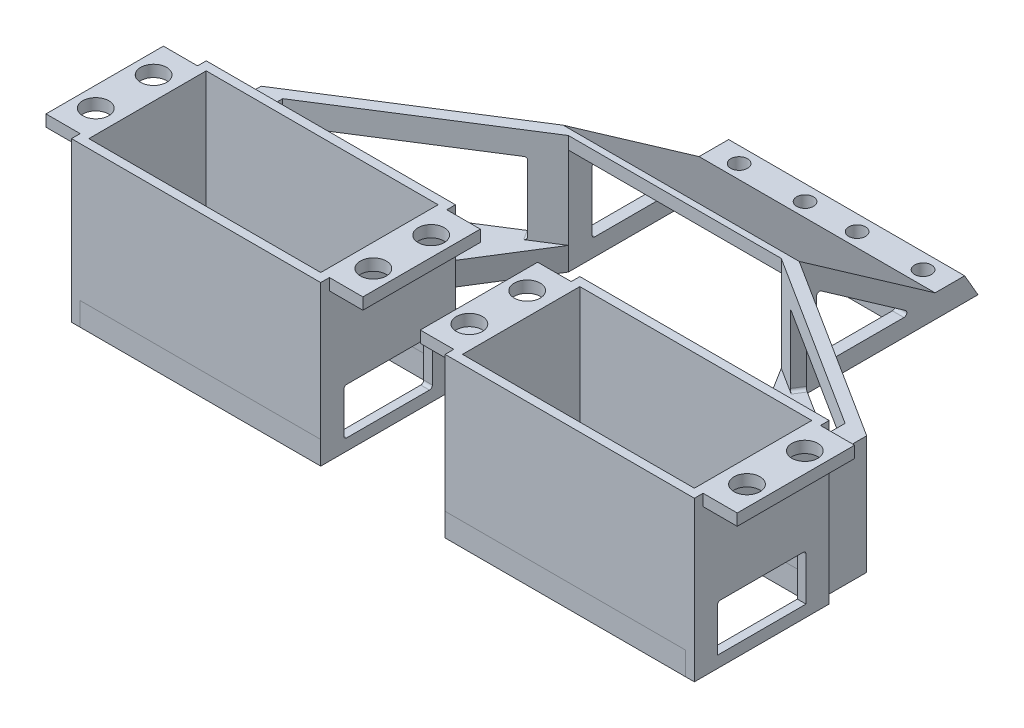
SolidWorks part; units mm, degrees
ref_plane "Front Plane" through (0, 0, 0) normal (0, 0, 1) x (1, 0, 0)
ref_plane "Top Plane" through (0, 0, 0) normal (0, 1, 0) x (1, 0, 0)
ref_plane "Right Plane" through (0, 0, 0) normal (1, 0, 0) x (0, 0, -1)
sketch "Sketch1" plane through (0, 0, 0) normal (0, 1, 0) x (1, 0, 0)
  line L0 (-59.76, 0) -> (59.76, 0) construction
  line L1 (0, -47.12) -> (0, 47.12) construction
  line L2 (-52.3548, -33.8709) -> (-52.3524, -13.5709)
  line L5 (-52.3524, -13.5709) -> (-12.2524, -13.5757)
  line L8 (-59.76, -47.12) -> (-59.76, -23.72) construction
  line L9 (-59.76, -47.12) -> (59.76, -47.12) construction
  line L10 (-59.76, -47.12) -> (-59.76, 47.12) construction
  line L11 (-59.76, 47.12) -> (59.76, 47.12) construction
  line L12 (59.76, -47.12) -> (59.76, 47.12) construction
  line L13 (-12.2524, -13.5757) -> (-12.2548, -33.8757)
  line L14 (-12.2548, -33.8757) -> (-52.3548, -33.8709)
  line L15 (-53.8522, -12.0707) -> (-10.7522, -12.0759)
  line L16 (-10.7522, -12.0759) -> (-10.755, -35.3759)
  line L17 (-10.755, -35.3759) -> (-53.855, -35.3707)
  line L18 (-53.855, -35.3707) -> (-53.8522, -12.0707)
  line L19 (-52.3524, -12.0709) -> (-52.3524, -4.0757)
  line L20 (-52.3524, -4.0757) -> (-12.2524, -4.0757)
  line L21 (-12.2524, -4.0757) -> (-12.2524, -12.0757)
  line L22 (-52.3548, -35.3709) -> (-52.3548, -43.3757)
  line L23 (-52.3548, -43.3757) -> (-12.2548, -43.3757)
  line L24 (-12.2548, -43.3757) -> (-12.2548, -35.3757)
  line L25 (-20.4049, 47.12) -> (0, 47.12)
  line L26 (-20.4049, 47.12) -> (-20.4049, 16.2008)
  line L27 (-20.4049, 16.2008) -> (-52.3524, -4.0757)
  line L28 (0, 47.12) -> (0, 45.12)
  line L29 (0, 45.12) -> (-18.4049, 45.12)
  line L30 (-18.4049, 45.12) -> (-18.4049, 15.1014)
  line L31 (-18.4049, 15.1014) -> (-48.6201, -4.0757)
  point P5 (0, 0)
  point P6 (0, 0)
  point P7 (-59.76, -23.72)
  point P32 (0, 47.12)
  line B0 (-52.3548, -33.8709) -> (-52.3524, -13.5709) construction
  line B1 (-4.9588, -13.5765) -> (-59.7588, -13.57) construction
  line B2 (-4.9612, -33.8765) -> (-4.9588, -13.5765) construction
  line B3 (-12.2548, -33.8757) -> (-12.2524, -13.5757) construction
  line B4 (-4.9612, -33.8765) -> (-59.7612, -33.87) construction
  line B5 (-59.7588, -13.57) -> (-59.7612, -33.87) construction
  circle B6 centre (-8.3042, -28.7261) radius 2.25 construction
  circle B7 centre (-8.303, -18.7261) radius 2.25 construction
  circle B8 centre (-56.303, -18.7204) radius 2.25 construction
  circle B9 centre (-56.3042, -28.7204) radius 2.25 construction
  dimension "D1" = 119.52
  dimension "D2" = 94.24
  dimension "D3" = 1.5
  dimension "D4" = 23.4
  dimension "D5" = 8
  dimension "D6" = 8
  dimension "D7" = 2
  dimension "D8" = 2
  dimension "D9" = 2
sketch_block_instance "Block2-1"
sketch_block "Block2"
extrude "Boss-Extrude1" add sketch "Sketch1" along normal blind 4 contours L31 L30 L29 L28 L25 L26 L27 L20 | L21 L20 L19 L15 | L18 L17 L16 L15 L13 L14 L2 L5 | L23 L24 L17 L22 region at (-53.1023, 0, 12.5608) region at (-32.3004, 0, 8.0745) region at (-35.9862, 0, -5.4443) region at (-32.3068, 0, 39.3745)
sketch "Sketch2" plane through (0, 4, 0) normal (0, 1, 0) x (1, 0, 0)
  line L1 (-48.6201, -4.0757) -> (-18.4049, 15.1014)
  line L2 (-18.4049, 15.1014) -> (-18.4049, 45.12)
  line L3 (-18.4049, 45.12) -> (0, 45.12)
  line L4 (0, 45.12) -> (0, 47.12)
  line L5 (0, 47.12) -> (-20.4049, 47.12)
  line L6 (-20.4049, 47.12) -> (-20.4049, 16.2008)
  line L7 (-20.4049, 16.2008) -> (-52.3524, -4.0757)
  line L8 (-53.8522, -12.0707) -> (-10.7522, -12.0759)
  line L9 (-10.7522, -12.0759) -> (-10.755, -35.3759)
  line L10 (-10.755, -35.3759) -> (-53.855, -35.3707)
  line L11 (-53.855, -35.3707) -> (-53.8522, -12.0707)
  line L12 (-48.6201, -4.0757) -> (-48.6201, -12.0713)
  line L13 (-52.3548, -33.8709) -> (-12.2524, -33.8709)
  line L14 (-52.3548, -33.8709) -> (-52.3548, -13.5757)
  line L15 (-52.3548, -13.5757) -> (-12.2524, -13.5757)
  line L16 (-12.2524, -33.8709) -> (-12.2524, -13.5757)
  line L17 (-52.3524, -4.0757) -> (-52.3524, -12.0709)
  point P30 (0, 0)
  line M1 (-48.6201, -4.0757) -> (-18.4049, 15.1014)
  line M2 (-18.4049, 15.1014) -> (-18.4049, 45.12)
  line M3 (-18.4049, 45.12) -> (0, 45.12)
  line M4 (0, 45.12) -> (0, 47.12)
  line M5 (0, 47.12) -> (-20.4049, 47.12)
  line M6 (-20.4049, 47.12) -> (-20.4049, 16.2008)
  line M7 (-20.4049, 16.2008) -> (-52.3524, -4.0757)
  line M8 (-52.3524, -4.0757) -> (-52.3524, -12.0709)
extrude "Boss-Extrude3" add sketch "Sketch2" along normal blind 23.5 contours L12 L8 M1 M2 M3 M4 M5 M6 M7 M8 | L8 L9 L10 L11 | L14 L15 L16 L13 region at (-49.4103, 4, 8.0735)
sketch "Sketch4" plane through (0, 27.5, 0) normal (0, 1, 0) x (1, 0, 0)
  line L0 (-52.3548, -13.5757) -> (-59.7588, -13.57)
  line L1 (-59.7588, -13.57) -> (-59.7612, -33.87)
  line L2 (-59.7612, -33.87) -> (-52.3548, -33.8709)
  line L3 (-12.2524, -13.5757) -> (-4.9588, -13.5765)
  line L4 (-4.9588, -13.5765) -> (-4.9612, -33.8765)
  line L5 (-4.9612, -33.8765) -> (-12.2524, -33.8709)
  line L6 (-12.2524, -33.8709) -> (-12.2524, -13.5757)
  line L7 (-52.3548, -33.8709) -> (-52.3548, -13.5757)
  circle A0 centre (-56.303, -18.7204) radius 2.25
  circle A1 centre (-56.3042, -28.7204) radius 2.25
  circle A2 centre (-8.303, -18.7261) radius 2.25
  circle A3 centre (-8.3042, -28.7261) radius 2.25
extrude "Boss-Extrude4" add sketch "Sketch4" against normal blind 2
sketch "Sketch5" plane through (-10.7507, 0, -0.0013) normal (1, 0, 0.0001) x (0.0001, 0, -1)
  line L1 (-31.3771, 2) -> (-16.0771, 2)
  line L2 (-31.3771, 2) -> (-31.3771, 10)
  line L3 (-31.3771, 10) -> (-16.0771, 10)
  line L4 (-16.0771, 2) -> (-16.0771, 10)
  line L6 (-35.3771, 27.5) -> (-35.3771, 0) construction
  line L7 (-12.0771, 27.5) -> (-12.0771, 0) construction
  line L8 (-13.5771, 0) -> (-33.8771, 0) construction
  dimension "D1" = 4
  dimension "D2" = 4
  dimension "D3" = 2
  dimension "D4" = 8
extrude "Cut-Extrude1" cut sketch "Sketch5" against normal through all
sketch "Sketch6" plane through (0, 4, 0) normal (0, 1, 0) x (1, 0, 0)
  line L0 (-52.3548, -43.3757) -> (-12.2548, -43.3757) construction
  line L1 (-12.2548, -43.3757) -> (-12.2548, -35.3757) construction
  line L2 (-52.3548, -35.3709) -> (-52.3548, -43.3757) construction
  line L3 (-52.3524, -12.0709) -> (-52.3524, -4.0757) construction
  line L4 (-52.3524, -4.0757) -> (-12.2524, -4.0757) construction
  line L5 (-12.2524, -4.0757) -> (-12.2524, -12.0757) construction
  circle A0 centre (-44.3548, -39.3757) radius 1.45
  circle A1 centre (-20.2548, -39.3757) radius 1.45
  circle A2 centre (-44.3524, -8.0757) radius 1.45
  circle A3 centre (-20.2524, -8.0757) radius 1.45
  dimension "D1" = 2.9
  dimension "D2" = 2.9
  dimension "D4" = 8
  dimension "D5" = 8
  dimension "D6" = 4
  dimension "D7" = 2.9
  dimension "D8" = 8
  dimension "D9" = 4
  dimension "D10" = 2.9
  dimension "D11" = 8
  dimension "D12" = 4
  dimension "D3" = 4
extrude "Cut-Extrude2" cut sketch "Sketch6" against normal through all
sketch "Sketch7" plane through (-20.4049, 0, 0) normal (-1, 0, 0) x (0, 0, 1)
  line L1 (-39.7008, 4) -> (-16.2008, 20.4549)
  line L3 (-16.2008, 27.5) -> (-16.2008, 0) construction
  line L5 (-16.2008, 20.4549) -> (12.0708, 20.4549)
  line L7 (12.0709, 38.4434) -> (-47.12, 27.5)
  line L8 (-47.12, 0) -> (-16.2008, 0) construction
  line L9 (-47.12, 4) -> (-39.7008, 4)
  line L10 (-47.12, 27.5) -> (-47.12, 0) construction
  line L13 (-47.12, 27.5) -> (-47.12, 4)
  line L14 (12.0709, 38.4434) -> (12.0707, 27.5)
  line L19 (12.0708, 20.4549) -> (12.0707, 27.5)
  dimension "D1" = 4
  dimension "D2" = 145
extrude "Cut-Extrude3" cut sketch "Sketch7" against normal through all and the other way through all
sketch "Sketch8" plane through (-20.4049, 0, 0) normal (-1, 0, 0) x (0, 0, 1)
  line L11 (-19.2008, 3) -> (-19.2008, 14.6919)
  line L12 (-19.2008, 3) -> (-19.2008, 14.6919)
  line L13 (-19.2008, 14.6919) -> (-35.8986, 3)
  line L14 (-35.8986, 3) -> (-19.2008, 3)
  line L18 (-35.8986, 3) -> (-19.2008, 3)
  line L21 (-19.2008, 14.6919) -> (-35.8986, 3)
  dimension "D1" = 3
extrude "Cut-Extrude4" cut sketch "Sketch8" against normal through all
sketch "Sketch9" plane through (0, 0, 0) normal (0, -1, 0) x (1, 0, 0)
  line L0 (0, -45.12) -> (0, -39.12)
  line L1 (0, -39.12) -> (-18.4049, -39.12)
  line L2 (-18.4049, -45.12) -> (-18.4049, -15.1014) construction
  line L3 (-18.4049, -39.12) -> (-18.4049, -45.12)
  line L4 (-18.4049, -45.12) -> (0, -45.12)
  dimension "D1" = 6
extrude "Boss-Extrude5" add sketch "Sketch9" against normal blind 4
sketch "Sketch10" plane through (0, 4, 0) normal (0, 1, 0) x (1, 0, 0)
  line L1 (-48.6201, -4.0757) -> (-12.2524, -4.0757) construction
  line L2 (-30.4362, -4.0757) -> (-48.6201, -4.0757)
  line L6 (-30.4362, -4.0757) -> (-18.4049, 15.1014)
  line L7 (-48.6201, -4.0757) -> (-18.4049, 15.1014)
extrude "Boss-Extrude6" add sketch "Sketch10" against normal blind 4
sketch "Sketch11" plane through (0, 3, 0) normal (0, 1, 0) x (1, 0, 0)
  line L0 (0, 39.12) -> (-18.4049, 39.12) construction
  line L1 (0, 47.12) -> (0, 39.12) construction
  line L3 (-20.4049, 39.7008) -> (-20.4049, 47.12) construction
  circle A0 centre (-15.9049, 42.12) radius 1.45
  circle A1 centre (-4.5, 42.12) radius 1.45
  dimension "D1" = 2.9
  dimension "D2" = 3
  dimension "D3" = 2.9
  dimension "D4" = 3
  dimension "D5" = 4.5
  dimension "D6" = 4.5
extrude "Cut-Extrude5" cut sketch "Sketch11" against normal through all and the other way through all
mirror "Mirror1" about plane through (0, 0, 0) normal (1, 0, 0) of "Boss-Extrude6", "Boss-Extrude5", "Cut-Extrude4", "Cut-Extrude3", "Cut-Extrude2", "Cut-Extrude1", "Boss-Extrude4", "Boss-Extrude3", "Boss-Extrude1", "Cut-Extrude5"
sketch "Sketch12" plane through (-13.1891, 0, -20.7806) normal (-0.5359, 0, -0.8443) x (-0.8443, 0, 0.5359)
  line L8 (42.3853, 4) -> (42.3853, 16.4549)
  line L9 (42.3853, 16.4549) -> (12.5465, 16.4549)
  line L10 (12.5465, 16.4549) -> (12.5465, 4)
  line L11 (12.5465, 4) -> (42.3853, 4)
  line L12 (42.3853, 4) -> (42.3853, 16.4549)
  line L14 (12.5465, 16.4549) -> (12.5465, 4)
  line L15 (12.5465, 4) -> (42.3853, 4)
  line L16 (42.3853, 16.4549) -> (12.5465, 16.4549)
  dimension "D1" = 4
extrude "Cut-Extrude6" cut sketch "Sketch12" against normal up to surface (2 mm away) up to face at (-33.5125, 12.2274, -5.5128)
fillet "Fillet1" radius 0.5 4 edges at (-23.2462, 4, -13.2131) (-48.4393, 4, 2.7765) (-48.4393, 16.4549, 2.7765) (-23.2462, 16.4549, -13.2131)
fillet "Fillet2" radius 0.5 3 edges at (-19.4049, 3, -35.8986) (-19.4049, 3, -19.2008) (-19.4049, 14.6919, -19.2008)
fillet "Fillet3" radius 0.5 8 edges at (-11.5027, 2, 16.0758) (-11.5045, 2, 31.3758) (-11.5034, 10, 31.3758) (-11.5025, 10, 16.0758) (-53.1027, 2, 16.0708) (-53.1045, 2, 31.3708) (-53.1046, 10, 31.3708) (-53.1037, 10, 16.0708)
sketch "Sketch13" plane through (13.1891, 0, -20.7806) normal (0.5359, 0, -0.8443) x (-0.8443, 0, -0.5359)
  line L8 (-12.5465, 4) -> (-12.5465, 16.4549)
  line L9 (-12.5465, 16.4549) -> (-42.3853, 16.4549)
  line L10 (-42.3853, 16.4549) -> (-42.3853, 4)
  line L11 (-42.3853, 4) -> (-12.5465, 4)
  line L12 (-12.5465, 4) -> (-12.5465, 16.4549)
  line L14 (-42.3853, 16.4549) -> (-42.3853, 4)
  line L15 (-42.3853, 4) -> (-12.5465, 4)
  line L16 (-12.5465, 16.4549) -> (-42.3853, 16.4549)
  dimension "D1" = 4
extrude "Cut-Extrude7" cut sketch "Sketch13" against normal up to surface (2 mm away) up to face at (33.5125, 12.2274, -5.5128)
fillet "Fillet4" radius 0.5 15 edges at (12.2534, 4, 31.3757) (12.2525, 4, 16.0757) (11.5025, 10, 16.0758) (11.5034, 10, 31.3758) (52.3537, 4, 16.0709) (53.1037, 10, 16.0708) (53.1046, 10, 31.3708) (52.3546, 4, 31.3709) (48.4393, 4, 2.7765) (48.4393, 16.4549, 2.7765) (23.2462, 16.4549, -13.2131) (23.2462, 4, -13.2131) (19.4049, 3, -19.2008) (19.4049, 14.6919, -19.2008) (19.4049, 3, -35.8986)
sketch "Sketch14" plane through (20.4049, 0, 0) normal (1, 0, 0) x (0, 0, -1)
  line L0 (47.12, 0) -> (44.8106, 4)
  line L1 (47.12, 4) -> (39.7008, 4) construction
  line L2 (44.8106, 4) -> (47.12, 4)
  line L3 (47.12, 4) -> (47.12, 0)
  line L4 (47.12, 0) -> (16.2008, 0) construction
  dimension "D1" = 60
extrude "Cut-Extrude8" cut sketch "Sketch14" against normal up to surface (40.8098 mm away) up to face at (-20.4049, 6.8853, -24.518)
sketch "Sketch15" plane through (0, 4, 0) normal (0, 1, 0) x (1, 0, 0)
  line L0 (-52.3548, -35.3709) -> (52.3548, -35.3709)
  line L1 (52.3548, -35.3709) -> (52.3548, -43.3757)
  line L2 (52.3548, -43.3757) -> (-52.3548, -43.3757)
  line L3 (-52.3548, -43.3757) -> (-52.3548, -35.3709)
extrude "Cut-Extrude9" cut sketch "Sketch15" against normal up to surface (4 mm away) up to face at (15.9049, 0, -40.67)
sketch "Sketch16" plane through (-18.4049, 0, 0) normal (1, 0, 0) x (0, 0, -1)
  line L0 (15.1014, 20.4549) -> (16.2008, 20.4549)
  line L1 (16.2008, 20.4549) -> (39.7008, 4)
  line L3 (35.4917, 4) -> (15.1014, 18.2775)
  line L4 (15.1014, 20.4549) -> (15.1014, 4) construction
  line L5 (15.1014, 18.2775) -> (15.1014, 20.4549)
  line L6 (35.4917, 4) -> (35.4917, 0)
  line L7 (39.12, 0) -> (15.1014, 0) construction
  line L8 (35.4917, 0) -> (39.12, 0)
  line L9 (39.12, 0) -> (39.12, 4)
  line L10 (39.12, 4) -> (39.7008, 4)
extrude "Boss-Extrude7" add sketch "Sketch16" along normal up to surface (36.8098 mm away) up to face at (18.4049, 6.8853, -24.518)
